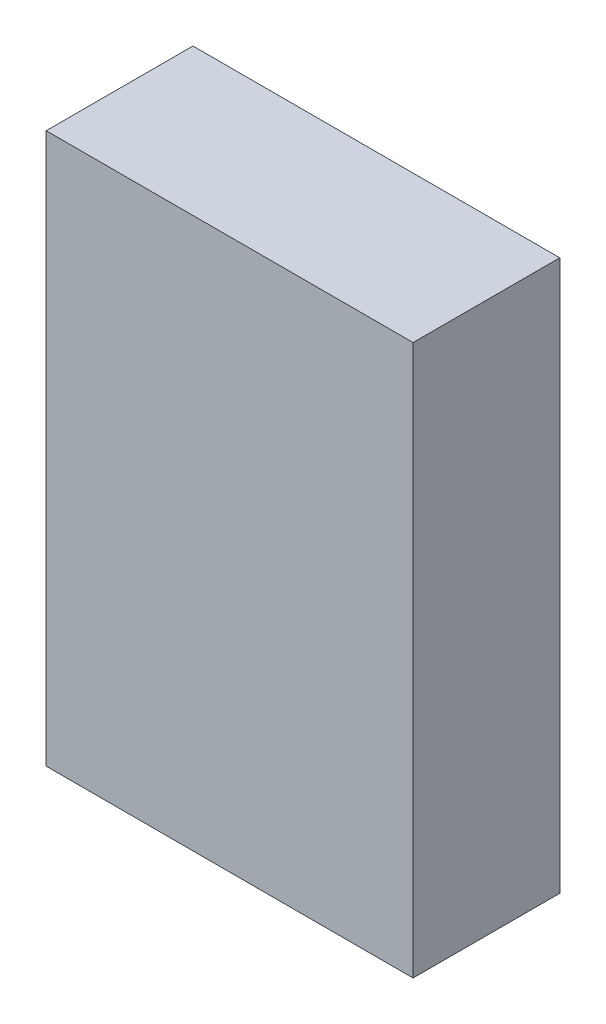
SolidWorks part; units mm, degrees
ref_plane "Plan de face" through (0, 0, 0) normal (0, 0, 1) x (1, 0, 0)
ref_plane "Plan de dessus" through (0, 0, 0) normal (0, 1, 0) x (1, 0, 0)
ref_plane "Plan de droite" through (0, 0, 0) normal (1, 0, 0) x (0, 0, -1)
sketch "Esquisse1" plane through (0, 0, 0) normal (0, 0, 1) x (1, 0, 0)
  line L1 (-56.626, 31.2883) -> (143.374, 31.2883)
  line L2 (-56.626, 31.2883) -> (-56.626, -268.7117)
  line L3 (-56.626, -268.7117) -> (143.374, -268.7117)
  line L4 (143.374, 31.2883) -> (143.374, -268.7117)
  dimension "D1" = 200
  dimension "D2" = 300
extrude "Boss.-Extru.1" add sketch "Esquisse1" along normal blind 80
shell "Coque1" thickness 6 removed face at (43.374, -118.7117, 0)
sketch "Esquisse3" plane through (0, 0, 0) normal (0, 0, -1) x (-1, 0, 0)
  line L8 (53.726, -265.8117) -> (53.726, 28.3883)
  line L9 (53.726, 28.3883) -> (-140.474, 28.3883)
  line L10 (-140.474, 28.3883) -> (-140.474, -265.8117)
  line L11 (-140.474, -265.8117) -> (53.726, -265.8117)
  line L12 (53.726, -265.8117) -> (53.726, 28.3883)
  line L13 (53.726, 28.3883) -> (-140.474, 28.3883)
  line L14 (-140.474, 28.3883) -> (-140.474, -265.8117)
  line L15 (-140.474, -265.8117) -> (53.726, -265.8117)
  dimension "D1" = 2.9
extrude "Enlèv. mat.-Extru.2" cut sketch "Esquisse3" against normal blind 6.1
sketch "Esquisse4" plane through (0, 0, 74) normal (0, 0, -1) x (-1, 0, 0)
  line L0 (13.126, -183.7117) -> (50.626, -183.7117)
  line L1 (50.626, 25.2883) -> (50.626, -262.7117) construction
  line L2 (13.126, -183.7117) -> (13.126, -262.7117)
  line L3 (50.626, -262.7117) -> (-137.374, -262.7117) construction
  line L4 (-99.874, -183.7117) -> (-137.374, -183.7117)
  line L5 (-99.874, -183.7117) -> (-99.874, -262.7117)
  line L6 (-137.374, -262.7117) -> (-137.374, 25.2883) construction
  line L8 (-99.874, -53.7117) -> (-137.374, -53.7117)
  line L9 (-99.874, -53.7117) -> (-99.874, 25.2883)
  line L10 (-137.374, 25.2883) -> (50.626, 25.2883) construction
  line L11 (13.126, -53.7117) -> (50.626, -53.7117)
  line L12 (13.126, -53.7117) -> (13.126, 25.2883)
  line L13 (-117.374, 5.2883) -> (-117.374, 25.2883)
  line L14 (-117.374, 25.2883) -> (-117.374, 5.2883)
  line L15 (-117.374, 5.2883) -> (-137.374, 5.2883)
  circle A0 centre (13.126, -183.7117) radius 9
  circle A1 centre (-99.874, -183.7117) radius 9
  circle A2 centre (13.126, -53.7117) radius 9
  circle A3 centre (-99.874, -53.7117) radius 9
  circle A4 centre (-117.374, 5.2883) radius 9
  dimension "D1" = 37.5
  dimension "D2" = 79
  dimension "D3" = 37.5
  dimension "D4" = 79
  dimension "D5" = 79
  dimension "D6" = 79
  dimension "D7" = 37.5
  dimension "D8" = 37.5
  dimension "D9" = 20
  dimension "D10" = 20
extrude "Boss.-Extru.2" add sketch "Esquisse4" along normal blind 67.9 contours A4
sketch "Esquisse5" plane through (0, 0, 6.1) normal (0, 0, -1) x (-1, 0, 0)
  circle A3 centre (-117.374, 5.2883) radius 2.5
  circle A4 centre (-117.374, 5.2883) radius 2.5
  dimension "D1" = 6.5
extrude "Enlèv. mat.-Extru.3" cut sketch "Esquisse5" against normal blind 30
extrude "Boss.-Extru.3" add sketch "Esquisse4<4>" along normal blind 15 contours L9 A3 L8 | L8 A3 L9 | L2 A0 L0 | L0 A0 L2 | A2 | A1 region at (-11.8528, -182.4384, 74) region at (-16.9458, -187.5314, 74) region at (98.6007, -54.9849, 74) region at (103.6937, -49.8919, 74)
sketch "Esquisse4<4>" plane through (0, 0, 74) normal (0, 0, -1) x (-1, 0, 0) same geometry as "Esquisse4"
sketch "Esquisse6" plane through (0, 0, 59) normal (0, 0, -1) x (-1, 0, 0)
  circle A3 centre (-99.874, -53.7117) radius 2.5
  circle A4 centre (-99.874, -53.7117) radius 2.5
  circle A6 centre (13.126, -53.7117) radius 2.5
  circle A7 centre (13.126, -53.7117) radius 2.5
  circle A9 centre (-99.874, -183.7117) radius 2.5
  circle A10 centre (-99.874, -183.7117) radius 2.5
  circle A12 centre (13.126, -183.7117) radius 2.5
  circle A13 centre (13.126, -183.7117) radius 2.5
  dimension "D1" = 6.5
  dimension "D2" = 6.5
  dimension "D3" = 6.5
  dimension "D4" = 6.5
extrude "Enlèv. mat.-Extru.6" cut sketch "Esquisse6" against normal blind 10
sketch "Esquisse8" plane through (0, 0, 74) normal (0, 0, -1) x (-1, 0, 0)
  line L0 (30.626, 5.2883) -> (50.626, 5.2883)
  line L1 (50.626, 25.2883) -> (50.626, -262.7117) construction
  line L2 (30.626, 5.2883) -> (30.626, 25.2883)
  line L3 (-137.374, 25.2883) -> (50.626, 25.2883) construction
  line L4 (30.626, -242.7117) -> (50.626, -242.7117)
  line L5 (30.626, -242.7117) -> (30.626, -262.7117)
  line L6 (50.626, -262.7117) -> (-137.374, -262.7117) construction
  line L7 (-117.374, -242.7117) -> (-137.374, -242.7117)
  line L8 (-137.374, -262.7117) -> (-137.374, 25.2883) construction
  line L9 (-117.374, -242.7117) -> (-117.374, -262.7117)
  circle A0 centre (30.626, 5.2883) radius 9
  circle A1 centre (30.626, -242.7117) radius 9
  circle A2 centre (-117.374, -242.7117) radius 9
  dimension "D1" = 20
  dimension "D2" = 20
  dimension "D3" = 20
  dimension "D4" = 20
  dimension "D5" = 20
  dimension "D6" = 20
extrude "Boss.-Extru.5" add sketch "Esquisse8" along normal blind 68 contours L0 A0 L2 | L2 A0 L0 | L5 A1 L4 | L4 A1 L5 | A2 region at (-34.4458, 9.1081, 74) region at (-29.3528, 4.0151, 74) region at (-29.3528, -241.4384, 74) region at (-34.4458, -246.5314, 74)
sketch "Esquisse9" plane through (0, 0, 6) normal (0, 0, -1) x (-1, 0, 0)
  circle A2 centre (30.626, 5.2883) radius 2.5
  circle A3 centre (30.626, 5.2883) radius 2.5
  circle A4 centre (30.626, -242.7117) radius 2.5
  circle A5 centre (30.626, -242.7117) radius 2.5
  circle A7 centre (-117.374, -242.7117) radius 2.5
  circle A8 centre (-117.374, -242.7117) radius 2.5
  dimension "D1" = 6.5
  dimension "D2" = 6.5
  dimension "D3" = 6.5
extrude "Enlèv. mat.-Extru.8" cut sketch "Esquisse9" against normal blind 30 contours A8 | A5 | A3
move or copy body "Corps-Déplacer/Copier1" bodies to move or copy 112 copy no translate (0, 114, 0)
move or copy body "Corps-Déplacer/Copier2" bodies to move or copy 143 copy no translate (0, 20, 0)
